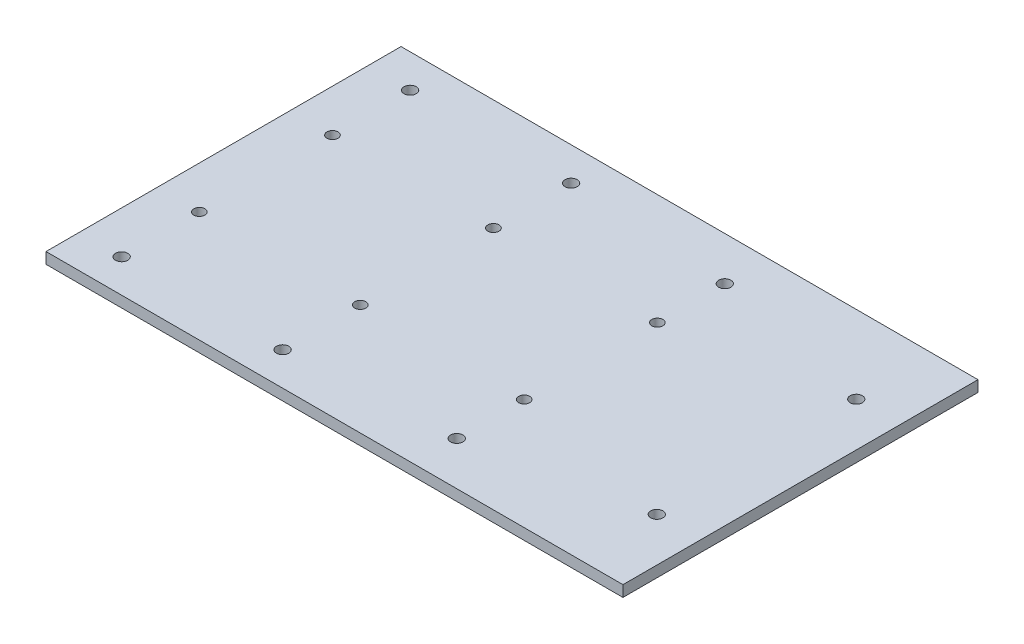
SolidWorks part; units mm, degrees
material "6061-T6 (SS)"
ref_plane "Front Plane" through (0, 0, 0) normal (0, 0, 1) x (1, 0, 0)
ref_plane "Top Plane" through (0, 0, 0) normal (0, 1, 0) x (1, 0, 0)
ref_plane "Right Plane" through (0, 0, 0) normal (1, 0, 0) x (0, 0, -1)
sketch "Sketch1" plane through (0, 0, 0) normal (0, 1, 0) x (1, 0, 0)
  line L1 (-165.1, -101.6) -> (165.1, -101.6)
  line L2 (-165.1, -101.6) -> (-165.1, 101.6)
  line L3 (-165.1, 101.6) -> (165.1, 101.6)
  line L4 (165.1, -101.6) -> (165.1, 101.6)
  line L5 (-165.1, -101.6) -> (165.1, 101.6) construction
  line L6 (-165.1, 101.6) -> (165.1, -101.6) construction
  point P0 (0, 0)
  dimension "D1" = 330.2
  dimension "D2" = 203.2
extrude "Boss-Extrude1" add sketch "Sketch1" along normal blind 6.35
sketch "Sketch2" plane through (0, 6.35, 0) normal (0, 1, 0) x (1, 0, 0)
  line L0 (-140.8516, 82.55) -> (-140.8516, -82.55) construction
  line L1 (-48.7159, 82.55) -> (-48.7159, -82.55) construction
  line L2 (45.0841, 76.699) -> (45.0841, -76.701) construction
  line L3 (-140.8516, 0) -> (45.0841, -0.001) construction
  line L4 (-140.8518, -38.1) -> (45.0839, -38.101) construction
  line L5 (-140.8514, 38.1) -> (45.0843, 38.099) construction
  point P0 (-140.8516, -82.55)
  point P1 (-48.7159, -82.55)
  point P3 (45.0841, -76.701)
  point P5 (45.0841, 76.699)
  point P7 (-48.7159, 82.55)
  point P9 (-140.8516, 82.55)
  point P25 (-48.7159, -38.1005)
  point P26 (-140.8518, -38.1)
  point P27 (-48.7159, 38.0995)
  point P28 (45.0843, 38.099)
  point P29 (45.0839, -38.101)
  point P30 (-140.8514, 38.1)
  point P31 (139.9541, 57.072)
  point P32 (139.9541, -57.072)
  dimension "D1" = 38.1
  dimension "D2" = 38.1
hole_wizard "1/4 (0.25) Press Dowel Hole1" positions "Sketch3" profile "Sketch4" hole size "1/4" standard "ANSI Inch" end condition through all
sketch "Sketch3" plane through (0, 6.35, 0) normal (0, 1, 0) x (1, 0, 0)
  point P0 (-140.8514, 38.1)
  point P3 (-140.8518, -38.1)
  point P6 (-48.7159, -38.1005)
  point P9 (-48.7159, 38.0995)
  point P12 (45.0843, 38.099)
  point P15 (45.0839, -38.101)
sketch "Sketch4" plane through (-140.8514, 6.35, -38.1) normal (1, 0, 0) x (0, 0, 1)
  line L0 (0, 0) -> (0, 6.35)
  line L1 (0, 6.35) -> (3.175, 6.35)
  line L2 (3.175, 6.35) -> (3.175, 0)
  line L5 (3.175, 0) -> (0, 0)
  line L11 (0, -6.35) -> (0, 107.95) construction
  dimension "Thru Hole Dia." = 6.35
  dimension "Thru Hole Depth" = 6.35
hole_wizard "M8x1.0 Tapped Hole1" positions "Sketch5" profile "Sketch6" tap size "M8x1.0" standard "ANSI Metric" end condition through all
sketch "Sketch5" plane through (0, 6.35, 0) normal (0, 1, 0) x (1, 0, 0)
  point P0 (-140.8516, 82.55)
  point P3 (-48.7159, 82.55)
  point P6 (45.0841, 76.699)
  point P9 (45.0841, -76.701)
  point P12 (-48.7159, -82.55)
  point P15 (-140.8516, -82.55)
  point P19 (139.9541, 57.072)
  point P22 (139.9541, -57.072)
sketch "Sketch6" plane through (-140.8516, 6.35, -82.55) normal (1, 0, 0) x (0, 0, 1)
  line L0 (0, 0) -> (0, 6.35)
  line L1 (0, 6.35) -> (3.5, 6.35)
  line L2 (3.5, 6.35) -> (3.5, 0)
  line L5 (3.5, 0) -> (0, 0)
  line L11 (0, -6.35) -> (0, 107.95) construction
  dimension "Thread Major Dia." = 7
  dimension "Thru Tap Drill Depth" = 6.35
sketch "Sketch7"
